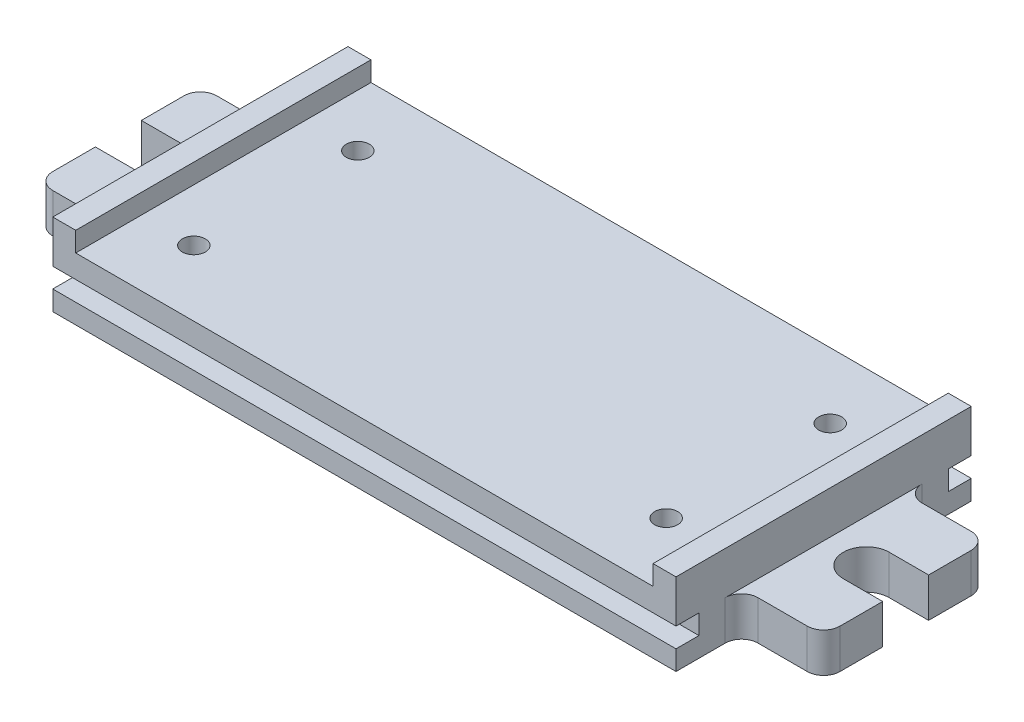
SolidWorks part; units mm, degrees
material "Gray Cast Iron"
ref_plane "Front Plane" through (0, 0, 0) normal (0, 0, 1) x (1, 0, 0)
ref_plane "Top Plane" through (0, 0, 0) normal (0, 1, 0) x (1, 0, 0)
ref_plane "Right Plane" through (0, 0, 0) normal (1, 0, 0) x (0, 0, -1)
sketch "Sketch1" plane through (0, 0, 0) normal (0, 1, 0) x (1, 0, 0)
  line L0 (88, 45) -> (88, -45)
  line L1 (-95, 45) -> (95, 45)
  line L2 (-95, 45) -> (-95, -45)
  line L3 (-95, -45) -> (95, -45)
  line L4 (95, 45) -> (95, -45)
  line L5 (-95, 45) -> (95, -45) construction
  line L6 (-95, -45) -> (95, 45) construction
  line L7 (-88, 45) -> (-88, -45)
  line L8 (0, 0) -> (0, -50000) construction
  line L9 (120, 25) -> (95, 25)
  line L10 (120, 25) -> (120, -25)
  line L11 (120, -25) -> (95, -25)
  line L12 (95, 25) -> (95, -25)
  line L13 (120, 25) -> (95, -25) construction
  line L14 (120, -25) -> (95, 25) construction
  line L15 (1.2733, 0) -> (50001.2733, 0) construction
  line L16 (120, 7) -> (108, 7)
  line L17 (108, -7) -> (120, -7)
  line L18 (-120, -25) -> (-95, 25) construction
  line L19 (-120, 25) -> (-95, -25) construction
  line L20 (-108, -7) -> (-120, -7)
  line L21 (-120, 7) -> (-108, 7)
  line L22 (-95, 25) -> (-95, -25)
  line L23 (-120, -25) -> (-95, -25)
  line L24 (-120, 25) -> (-120, -25)
  line L25 (-120, 25) -> (-95, 25)
  line L27 (-77, 30) -> (77, 30)
  line L28 (-82, 25) -> (-82, -25)
  line L29 (-77, -30) -> (77, -30)
  line L30 (82, 25) -> (82, -25)
  line L31 (-82, 30) -> (82, -30) construction
  line L32 (-82, -30) -> (82, 30) construction
  arc A0 (108, 7) -> (108, -7) centre (108, 0) ccw
  arc A1 (-108, 7) -> (-108, -7) centre (-108, 0) cw
  arc A2 (77, 30) -> (82, 25) centre (77, 25) cw
  arc A3 (77, -30) -> (82, -25) centre (77, -25) ccw
  arc A4 (-82, -25) -> (-77, -30) centre (-77, -25) ccw
  arc A5 (-77, 30) -> (-82, 25) centre (-77, 25) ccw
  point P0 (0, 0)
  point P10 (107.5, 0)
  point P25 (101, 0)
  point P35 (-107.5, 0)
  point P36 (0, 0)
  dimension "D11" = 5
  dimension "D1" = 190
  dimension "D2" = 90
  dimension "D3" = 7
  dimension "D4" = 7
  dimension "D5" = 50
  dimension "D6" = 25
  dimension "D7" = 19
  dimension "D8" = 14
  dimension "D9" = 164
  dimension "D10" = 60
extrude "Boss-Extrude1" add sketch "Sketch1" along normal blind 25 contours L4 L1 L0 L3 | L7 L1 L2 L3 region at (91.5, 0, 0) region at (-91.5, 0, 0)
extrude "Boss-Extrude2" add sketch "Sketch1<3>" along normal blind 19 contours L27 A5 L28 A4 L29 A3 L30 A2 | L1 L7 L3 L0 A5 L27 A2 L30 A3 L29 A4 L28 region at (86.0232, 0, 0) region at (0, 0, 0)
sketch "Sketch1<3>" plane through (0, 0, 0) normal (0, 1, 0) x (1, 0, 0) same geometry as "Sketch1"
extrude "Boss-Extrude3" add sketch "Sketch1<4>" along normal blind 12 contours A0 L16 L10 L9 L4 L11 L17 | L21 A1 L20 L24 L23 L2 L25 region at (107.5, 0, -24.441) region at (-95.559, 0, 0)
sketch "Sketch1<4>" plane through (0, 0, 0) normal (0, 1, 0) x (1, 0, 0) same geometry as "Sketch1"
extrude "Cut-Extrude1" cut sketch "Sketch1<5>" along normal blind 6 contours L27 A5 L28 A4 L29 A3 L30 A2 region at (0, 0, 0)
sketch "Sketch1<5>" plane through (0, 0, 0) normal (0, 1, 0) x (1, 0, 0) same geometry as "Sketch1"
sketch "Sketch2" plane through (95, 0, 0) normal (1, 0, 0) x (0, 0, -1)
  line L0 (0, 0) -> (0, -50000) construction
  line L1 (45, 25) -> (45, 0) construction
  line L2 (38, 12) -> (45, 12)
  line L3 (38, 12) -> (38, 6)
  line L4 (38, 6) -> (45, 6)
  line L5 (45, 12) -> (45, 6)
  line L6 (-45, 12) -> (-45, 6)
  line L7 (-38, 6) -> (-45, 6)
  line L8 (-38, 12) -> (-38, 6)
  line L9 (-38, 12) -> (-45, 12)
  line L10 (45, 0) -> (25, 0) construction
  dimension "D1" = 6
  dimension "D2" = 6
  dimension "D3" = 7
extrude "Cut-Extrude2" cut sketch "Sketch2" against normal up to next
hole_wizard "M8x1.0 Tapped Hole1" positions "Sketch3" profile "Sketch4" tap size "M8x1.0" standard "ANSI Metric" end condition up to next
sketch "Sketch3" plane through (0, 19, 0) normal (0, 1, 0) x (1, 0, 0)
  line L0 (88, 45) -> (88, -45) construction
  point P0 (72, -25)
  dimension "D1" = 25
  dimension "D2" = 16
sketch "Sketch4" plane through (72, 19, 25) normal (1, 0, 0) x (0, 0, 1)
  line L0 (0, 0) -> (0, 13)
  line L1 (0, 13) -> (3.5, 13)
  line L2 (3.5, 13) -> (3.5, 0)
  line L5 (3.5, 0) -> (0, 0)
  line L11 (0, -6.35) -> (0, 107.95) construction
  dimension "Thru Tap Drill Dia." = 7
  dimension "Thru Tap Drill Depth" = 13
cosmetic thread "Hole Thread1" parameters "D2"=8
pattern_linear "LPattern1" count 2 spacing 50 along (0, 0, -1) count 2 spacing 144 along (-1, 0, 0) of "M8x1.0 Tapped Hole1"
cosmetic thread "Hole Thread2" parameters "D2"=8
cosmetic thread "Hole Thread3" parameters "D2"=8
cosmetic thread "Hole Thread4" parameters "D2"=8
fillet "Fillet1" radius 5 8 edges at (-95, 6, -25) (-120, 6, -25) (-120, 6, 25) (-95, 6, 25) (95, 6, -25) (120, 6, -25) (95, 6, 25) (120, 6, 25)
